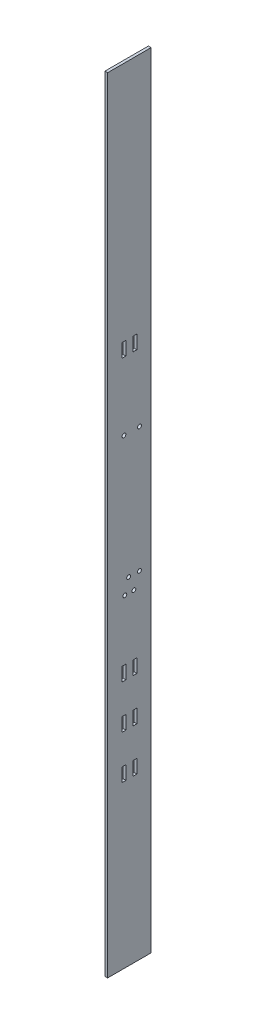
SolidWorks part; units mm, degrees
ref_plane "Front Plane" through (0, 0, 0) normal (0, 0, 1) x (1, 0, 0)
ref_plane "Top Plane" through (0, 0, 0) normal (0, 1, 0) x (1, 0, 0)
ref_plane "Right Plane" through (0, 0, 0) normal (1, 0, 0) x (0, 0, -1)
sketch "Sketch1" plane through (0, 0, 0) normal (1, 0, 0) x (0, 0, -1)
  line L1 (-25.4, 457.2) -> (25.4, 457.2)
  line L2 (-25.4, 457.2) -> (-25.4, -457.2)
  line L3 (-25.4, -457.2) -> (25.4, -457.2)
  line L4 (25.4, 457.2) -> (25.4, -457.2)
  line L5 (-25.4, 457.2) -> (25.4, -457.2) construction
  line L6 (-25.4, -457.2) -> (25.4, 457.2) construction
  point P0 (0, 0)
  dimension "D1" = 914.4
  dimension "D2" = 50.8
extrude "Boss-Extrude1" add sketch "Sketch1" along normal blind 3.175
sketch "Sketch2" plane through (3.175, 0, 0) normal (1, 0, 0) x (0, 0, -1)
  line L0 (-25.4, -457.2) -> (25.4, -457.2) construction
  line L1 (4, -201.6125) -> (8.7625, -201.6125)
  line L2 (4, -201.6125) -> (4, -217.4875)
  line L3 (4, -217.4875) -> (8.7625, -217.4875)
  line L4 (8.7625, -201.6125) -> (8.7625, -217.4875)
  line L5 (4, -201.6125) -> (8.7625, -217.4875) construction
  line L6 (4, -217.4875) -> (8.7625, -201.6125) construction
  point P0 (6.3813, -209.55)
  dimension "D1" = 4.7625
  dimension "D2" = 15.875
  dimension "D3" = 239.7125
  dimension "D4" = 4
extrude "Cut-Extrude1" cut sketch "Sketch2" against normal through all
mirror "Mirror1" about plane through (0, 0, 0) normal (0, 0, 1) of "Cut-Extrude1"
pattern_linear "LPattern1" count 2 spacing 50.8 along (0, 1, 0) count 2 spacing 50.8 along (0, -1, 0) of "Mirror1"
sketch "Sketch3" plane through (3.175, 0, 0) normal (1, 0, 0) x (0, 0, -1)
  line L0 (8.7625, -150.8125) -> (4, -150.8125) construction
  line L1 (4, 176.2125) -> (8.7625, 176.2125)
  line L2 (4, 176.2125) -> (4, 160.3375)
  line L3 (4, 160.3375) -> (8.7625, 160.3375)
  line L4 (8.7625, 176.2125) -> (8.7625, 160.3375)
  line L5 (4, 176.2125) -> (8.7625, 160.3375) construction
  line L6 (4, 160.3375) -> (8.7625, 176.2125) construction
  line L7 (8.7625, -166.6875) -> (8.7625, -150.8125) construction
  line L8 (4, -150.8125) -> (4, -166.6875) construction
  line L9 (0, 0) -> (0, 53.0447) construction
  line L10 (-4, 160.3375) -> (-8.7625, 176.2125) construction
  line L11 (-4, 176.2125) -> (-8.7625, 160.3375) construction
  line L12 (-8.7625, 176.2125) -> (-8.7625, 160.3375)
  line L13 (-4, 160.3375) -> (-8.7625, 160.3375)
  line L14 (-4, 176.2125) -> (-4, 160.3375)
  line L15 (-4, 176.2125) -> (-8.7625, 176.2125)
  point P0 (6.3812, 168.275)
  point P12 (6.3812, 160.3375)
  point P19 (-6.3812, 168.275)
  dimension "D1" = 311.15
extrude "Cut-Extrude2" cut sketch "Sketch3" against normal through all
hole_wizard "#8 Clearance Hole1" positions "Sketch4" profile "Sketch5" hole size "#8" standard "ANSI Inch" end condition through all
sketch "Sketch4" plane through (3.175, 0, 0) normal (1, 0, 0) x (0, 0, -1)
  point P0 (11.827, -64.5237)
  point P3 (-0.873, -64.5237)
  point P6 (11.827, 81.272)
  point P9 (-6.35, 81.272)
  point P12 (5.25, -80.7656)
  point P15 (-5.25, -80.7656)
sketch "Sketch5" plane through (3.175, -64.5237, -11.827) normal (0, 1, 0) x (0, 0, -1)
  line L0 (0, 0) -> (0, 3.175)
  line L1 (0, 3.175) -> (2.2479, 3.175)
  line L2 (2.2479, 3.175) -> (2.2479, 0)
  line L5 (2.2479, 0) -> (0, 0)
  line L11 (0, -6.35) -> (0, 107.95) construction
  dimension "Thru Hole Dia." = 4.4958
  dimension "Thru Hole Depth" = 3.175
